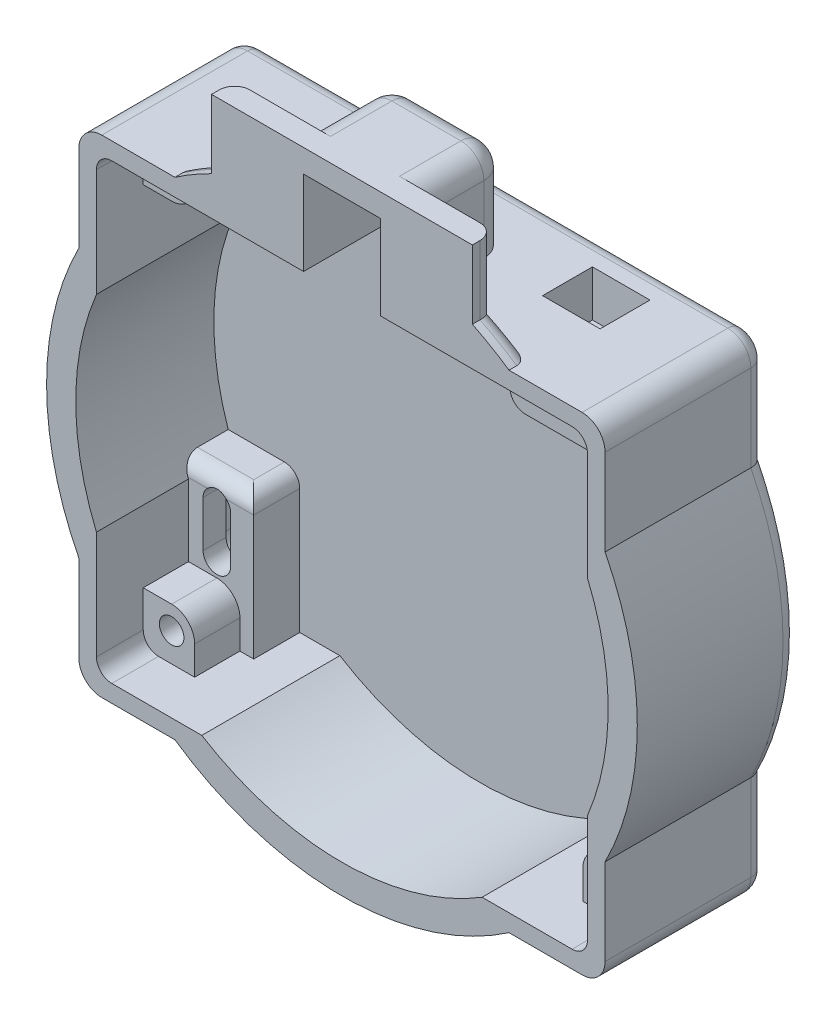
SolidWorks part; units mm, degrees
ref_plane "Front Plane" through (0, 0, 0) normal (0, 0, 1) x (1, 0, 0)
ref_plane "Top Plane" through (0, 0, 0) normal (0, 1, 0) x (1, 0, 0)
ref_plane "Right Plane" through (0, 0, 0) normal (1, 0, 0) x (0, 0, -1)
sketch "Sketch1" plane through (0, 0, 0) normal (0, 0, 1) x (1, 0, 0)
  line L0 (0, 50.5271) -> (0, -52.5058) construction
  line L1 (-17, 43.5) -> (-17, 34.5435)
  line L2 (-17, 43.5) -> (17, 43.5)
  line L3 (17, 43.5) -> (17, 34.5435)
  line L4 (-47.9319, 0) -> (53.9746, 0) construction
  line L5 (-18.2713, 29.5) -> (18.2713, 29.5)
  line L6 (34.3, 31.75) -> (21.7758, 31.75)
  line L7 (34.3, 31.75) -> (34.3, 17.486)
  line L8 (-34.3, 31.75) -> (-34.3, 17.486)
  line L9 (-34.3, 31.75) -> (-21.7758, 31.75)
  line L10 (34.3, -31.75) -> (34.3, -17.486)
  line L11 (34.3, -31.75) -> (21.7758, -31.75)
  line L12 (-34.3, -31.75) -> (-34.3, -17.486)
  line L13 (-34.3, -31.75) -> (-21.7758, -31.75)
  circle A0 centre (0, 0) radius 33.5 construction
  circle A1 centre (0, 0) radius 34.7
  circle A3 centre (0, 0) radius 38.2616 construction
  circle A5 centre (-28.3, 25.75) radius 1.6
  circle A8 centre (28.3, 25.75) radius 1.6
  circle A10 centre (28.3, -25.75) radius 1.6
  circle A12 centre (-28.3, -25.75) radius 1.6
  circle A19 centre (11, 38.1456) radius 1.6 construction
  circle A20 centre (-11, 38.1456) radius 1.6 construction
  arc A21 (21.7758, 31.75) -> (-21.7758, 31.75) centre (0, 0) ccw
  arc A22 (34.3, -17.486) -> (34.3, 17.486) centre (0, 0) ccw
  arc A23 (-21.7758, -31.75) -> (21.7758, -31.75) centre (0, 0) ccw
  arc A24 (-34.3, 17.486) -> (-34.3, -17.486) centre (0, 0) ccw
  dimension "D1" = 67
  dimension "D9" = 3.2
  dimension "D14" = 3.2
  dimension "D3" = 77
  dimension "D2" = 1.2
  dimension "D4" = 34
  dimension "D5" = 10
  dimension "D7" = 25.75
  dimension "D8" = 28.3
  dimension "D12" = 5
  dimension "D13" = 6
  dimension "D15" = 29.5
  dimension "D16" = 6
  dimension "D17" = 6
extrude "Boss-Extrude5" add sketch "Sketch1" along normal blind 3 contours A24 A22 A19 A20 A8 A5 A1 A10 A12 | L1 A20 A19 L3 L2 | L5 A1 | L5 A1 | A12 region at (0, 40.2459, 0) region at (0, 37.4111, 0) region at (0, 31.594, 0) region at (0, -1.1129, 0)
extrude "Boss-Extrude6" add sketch "Sketch1<8>" along normal blind 21 contours L5 A1 | L1 A20 A19 L3 L2 | A24 A22 A19 A20 A8 A5 A1 A10 A12 | A12 region at (0, 40.2459, 0) region at (0, 37.4111, 0) region at (0, 31.594, 0) region at (-28.3, -25.75, 0)
sketch "Sketch1<8>" plane through (0, 0, 0) normal (0, 0, 1) x (1, 0, 0) same geometry as "Sketch1"
sketch "Sketch4" plane through (0, 0, 0) normal (0, 0, -1) x (-1, 0, 0)
  line L7 (-21.7758, 43.5) -> (21.7758, 43.5)
  line L12 (-21.7758, 43.5) -> (-21.7758, 31.75)
  line L13 (-21.7758, 31.75) -> (21.7758, 31.75)
  line L14 (21.7758, 31.75) -> (21.7758, 43.5)
  line L16 (17, 43.5) -> (-17, 43.5) construction
extrude "Cut-Extrude3" cut sketch "Sketch4" against normal blind 7
ref_plane "Plane1" through (0, 43.5, 0) normal (0, 1, 0) x (1, 0, 0)
sketch "Sketch6" plane through (0, 43.5, 0) normal (0, 1, 0) x (1, 0, 0)
  line L1 (-20.5, -9.5) -> (-9.5, -9.5)
  line L2 (-20.5, -9.5) -> (-20.5, -15.5)
  line L3 (-20.5, -15.5) -> (-9.5, -15.5)
  line L4 (-9.5, -9.5) -> (-9.5, -15.5)
  line L5 (-17, -21) -> (17, -21) construction
  line L8 (-31.5, -18.7445) -> (31.5, -18.7445) construction
  line L11 (0, 9.1514) -> (0, -26.2112) construction
  line L12 (21.7758, -7) -> (-21.7758, -7) construction
  line L13 (-7.5, -7) -> (-38.5, -7)
  line L14 (-7.5, -7) -> (-7.5, -18)
  line L15 (-7.5, -18) -> (-38.5, -18)
  line L16 (-38.5, -7) -> (-38.5, -18)
  line L18 (-38.5, 0) -> (-38.5, -21) construction
  line L19 (38.5, -7) -> (38.5, -18)
  line L20 (7.5, -18) -> (38.5, -18)
  line L21 (7.5, -7) -> (38.5, -7)
  line L22 (7.5, -7) -> (7.5, -18)
  line M8 (17, -7) -> (-17, -7)
  line M9 (-17, -7) -> (-17, -21)
  dimension "D1" = 11
  dimension "D2" = 6
  dimension "D3" = 5.5
  dimension "D4" = 63
  dimension "D5" = 22
  dimension "D6" = 2
  dimension "D7" = 3
extrude "Cut-Extrude5" cut sketch "Sketch6" against normal up to surface (11.75 mm away) contours L4 L1 L3 M9 | L2 L3 L1 M9 | L15 L14 L1 L4 L3 M8 M9 | L13 L16 L15 L3 L2 L1 M9 | L19 L20 L22 L21 region at (-28.627, 43.5, 12.5) region at (-18.75, 43.5, 12.5) region at (-16.8547, 43.5, 8.25) region at (-13.25, 43.5, 12.5) up to face at (0, 31.75, 12.25)
extrude "Cut-Extrude6" cut sketch "Sketch6<4>" against normal blind 40 contours L4 L1 L3 M9 | L2 L3 L1 M9 region at (-18.75, 43.5, 12.5) region at (-13.25, 43.5, 12.5)
sketch "Sketch6<4>" plane through (0, 43.5, 0) normal (0, 1, 0) x (1, 0, 0) same geometry as "Sketch6"
sketch "Sketch8" plane through (0, 0, 0) normal (1, 0, 0) x (0, 0, -1)
  line L0 (-7, 31.75) -> (-7, 43.5) construction
  line L1 (-21, 40.5) -> (-10, 40.5)
  line L2 (-21, 40.5) -> (-21, 24.5)
  line L3 (-21, 24.5) -> (-10, 24.5)
  line L4 (-10, 40.5) -> (-10, 24.5)
  line L5 (-7, 43.5) -> (-18, 43.5) construction
  line L6 (-21, 43.5) -> (-21, 34.5435) construction
  dimension "D1" = 3
  dimension "D2" = 16
  dimension "D3" = 3
extrude "Cut-Extrude7" cut sketch "Sketch8" against normal blind 5 and the other way blind 5
sketch "Sketch9" plane through (0, 0, 21) normal (0, 0, 1) x (1, 0, 0)
  line L0 (0, 46.0396) -> (0, -47.6763) construction
  line L1 (-55.9016, 0) -> (68.9785, 0) construction
  line L3 (-32, 29.5) -> (32, 29.5)
  line L4 (-32, 29.5) -> (-32, -29.5)
  line L5 (-32, -29.5) -> (32, -29.5)
  line L6 (32, 29.5) -> (32, -29.5)
  dimension "D1" = 64
  dimension "D2" = 59
extrude "Cut-Extrude8" cut sketch "Sketch9" against normal blind 6.1
sketch "Sketch12" plane through (0, 0, 14.9) normal (0, 0, 1) x (1, 0, 0)
  line L0 (0, 47.9752) -> (0, -48.7077) construction
  line L1 (-25.3, 29.5) -> (-18, 29.5)
  line L2 (-32, 22.75) -> (-32, 11.5)
  line L3 (-32, 11.5) -> (-18, 11.5)
  line L4 (-18, 29.5) -> (-18, 11.5)
  line L5 (-46.551, 0) -> (53.7127, 0) construction
  line L18 (-28.3, 22.75) -> (-32, 22.75)
  line L19 (-25.3, 25.75) -> (-25.3, 29.5)
  line L21 (-32, 29.5) -> (-32, 13.4198) construction
  line L22 (28.3, 22.75) -> (32, 22.75)
  line L23 (25.3, 25.75) -> (25.3, 29.5)
  line L24 (25.3, 29.5) -> (18, 29.5)
  line L25 (18, 29.5) -> (18, 11.5)
  line L26 (32, 11.5) -> (18, 11.5)
  line L27 (32, 22.75) -> (32, 11.5)
  line L28 (-28.3, -22.75) -> (-32, -22.75)
  line L29 (-25.3, -25.75) -> (-25.3, -29.5)
  line L30 (-25.3, -29.5) -> (-18, -29.5)
  line L31 (-18, -29.5) -> (-18, -11.5)
  line L32 (-32, -11.5) -> (-18, -11.5)
  line L33 (-32, -22.75) -> (-32, -11.5)
  line L34 (28.3, -22.75) -> (32, -22.75)
  line L35 (32, -22.75) -> (32, -11.5)
  line L36 (32, -11.5) -> (18, -11.5)
  line L37 (18, -29.5) -> (18, -11.5)
  line L38 (25.3, -29.5) -> (18, -29.5)
  line L39 (25.3, -25.75) -> (25.3, -29.5)
  line L40 (-5, 29.5) -> (-32, 29.5) construction
  arc A0 (-28.3, 22.75) -> (-25.3, 25.75) centre (-28.3, 25.75) ccw
  arc A5 (28.3, 22.75) -> (25.3, 25.75) centre (28.3, 25.75) cw
  arc A6 (-28.3, -22.75) -> (-25.3, -25.75) centre (-28.3, -25.75) cw
  arc A7 (28.3, -22.75) -> (25.3, -25.75) centre (28.3, -25.75) ccw
  dimension "D1" = 6
  dimension "D2" = 18
  dimension "D3" = 14
  dimension "D4" = 29.5
extrude "Cut-Extrude11" cut sketch "Sketch12" against normal up to surface (11.9 mm away) up to face at (0, -2.6, 3)
sketch "Sketch13" plane through (0, 0, 0) normal (0, 0, -1) x (-1, 0, 0)
  line L0 (34.3, -31.75) -> (23.5, -31.75)
  line L1 (34.3, -31.75) -> (21.7758, -31.75) construction
  line L2 (23.5, -31.75) -> (23.5, -11.25)
  line L3 (23.5, -11.25) -> (36.8197, -11.25)
  line L4 (34.3, -31.75) -> (34.3, -17.486)
  line L5 (28.3, -20.55) -> (28.3, -14.55) construction
  line L6 (26.5, -20.55) -> (26.5, -14.55)
  line L7 (30.1, -20.55) -> (30.1, -14.55)
  line L9 (25.05, -11.8) -> (31.55, -11.8)
  line L10 (25.05, -11.8) -> (25.05, -23.3)
  line L11 (25.05, -23.3) -> (31.55, -23.3)
  line L12 (31.55, -11.8) -> (31.55, -23.3)
  line L13 (25.05, -11.8) -> (31.55, -23.3) construction
  line L14 (25.05, -23.3) -> (31.55, -11.8) construction
  arc A0 (34.3, -17.486) -> (34.3, 17.486) centre (0, 0) ccw construction
  arc A1 (36.8197, -11.25) -> (34.3, -17.486) centre (0, 0) cw
  arc A2 (26.5, -20.55) -> (30.1, -20.55) centre (28.3, -20.55) ccw
  arc A3 (30.1, -14.55) -> (26.5, -14.55) centre (28.3, -14.55) ccw
  point P13 (28.3, -12.75)
  point P17 (28.3, -17.55)
  point P23 (28.3, -22.35)
  point P25 (28.3, -17.55)
  line M16 (21.7758, -31.75) -> (34.3, -31.75)
  line M17 (34.3, -31.75) -> (34.3, -17.486)
  arc M18 (34.3, -17.486) -> (34.3, 17.486) centre (0, 0) ccw
  dimension "D2" = 9.6
  dimension "D1" = 3.6
  dimension "D3" = 3
  dimension "D4" = 1.5
  dimension "D5" = 3.4
  dimension "D6" = 6.5
  dimension "D7" = 11.5
extrude "Boss-Extrude8" add sketch "Sketch13" against normal blind 6 from offset 3 contours L3 L2 L9 L12 L11 L10 M16 M17 M18 | L12 L9 L10 L11 A3 L7 A2 L6 | L7 A3 L6 A2 region at (-28.9, -31.5055, 0) region at (-28.3, -17.55, 0) region at (-28.3, -11.9321, 0) offset against normal yes
extrude "Cut-Extrude12" cut sketch "Sketch13<4>" against normal through all contours L7 A3 L6 A2 region at (-28.3, -17.55, 0)
sketch "Sketch13<4>" plane through (0, 0, 0) normal (0, 0, -1) x (-1, 0, 0) same geometry as "Sketch13"
extrude "Cut-Extrude13" cut sketch "Sketch13<6>" against normal blind 6 contours L12 L9 L10 L11 A3 L7 A2 L6 region at (-28.3, -11.9321, 0)
sketch "Sketch13<6>" plane through (0, 0, 0) normal (0, 0, -1) x (-1, 0, 0) same geometry as "Sketch13"
sketch "Sketch15" plane through (0, 31.75, 0) normal (0, 1, 0) x (1, 0, 0)
  line L0 (32, -14.9) -> (25.3, -14.9) construction
  line L1 (13.3, 0) -> (25.3, 0)
  line L2 (13.3, 0) -> (13.3, -12.4)
  line L3 (13.3, -12.4) -> (25.3, -12.4)
  line L4 (25.3, 0) -> (25.3, -12.4)
  line L5 (25.3, -3) -> (25.3, -14.9) construction
  line L6 (-21.7758, 0) -> (21.7758, 0) construction
  line L7 (19.3, -12.4) -> (19.3, -2.9681) construction
  line L8 (16.4, -4.6) -> (22.2, -4.6)
  line L9 (16.4, -4.6) -> (16.4, -10.4)
  line L10 (16.4, -10.4) -> (22.2, -10.4)
  line L11 (22.2, -4.6) -> (22.2, -10.4)
  line L12 (16.4, -10.4) -> (15.55, -10.4)
  line L13 (15.55, -10.4) -> (15.55, -3.9)
  line L14 (15.55, -3.9) -> (23.05, -3.9)
  line L15 (23.05, -3.9) -> (23.05, -10.4)
  line L16 (23.05, -10.4) -> (22.2, -10.4)
  line M39 (34.3, 0) -> (-34.3, 0)
  dimension "D1" = 2.5
  dimension "D2" = 12
  dimension "D3" = 5.8
  dimension "D4" = 7.5
  dimension "D5" = 6.5
  dimension "D6" = 2
extrude "Boss-Extrude10" add sketch "Sketch15" against normal blind 12.5 contours L10 L7 L8 L9 | L7 L10 L11 L8 | L8 L7 L14 L13 L12 L9 | L7 L8 L11 L16 L15 L14 | L4 L2 L3 L10 L12 L13 L14 L15 L16 M39 region at (17.85, 31.75, 7.5) region at (20.75, 31.75, 7.5) region at (19.3, 31.75, 0.1726) region at (17.85, 31.75, 4.525) region at (19.375, 31.75, 4.25)
extrude "Cut-Extrude14" cut sketch "Sketch15<3>" against normal blind 6 contours L8 L7 L14 L13 L12 L9 | L7 L8 L11 L16 L15 L14 region at (17.85, 31.75, 4.525) region at (19.375, 31.75, 4.25)
sketch "Sketch15<3>" plane through (0, 31.75, 0) normal (0, 1, 0) x (1, 0, 0) same geometry as "Sketch15"
extrude "Cut-Extrude15" cut sketch "Sketch15<4>" against normal up to next contours L7 L10 L11 L8 | L10 L7 L8 L9 region at (17.85, 31.75, 7.5) region at (20.75, 31.75, 7.5)
sketch "Sketch15<4>" plane through (0, 31.75, 0) normal (0, 1, 0) x (1, 0, 0) same geometry as "Sketch15"
extrude "Cut-Extrude16" cut sketch "Sketch1<9>" along normal through all contours A12 region at (-28.3, -25.75, 0)
sketch "Sketch1<9>" plane through (0, 0, 0) normal (0, 0, 1) x (1, 0, 0) same geometry as "Sketch1"
fillet "Fillet1" radius 3 11 edges at (-34.3, 31.75, 10.5) (-34.3, -31.75, 10.5) (34.3, -31.75, 10.5) (34.3, 31.75, 10.5) (-7.5, 37.625, 7) (7.5, 37.625, 7) (0, 43.5, 7) (-7.5, 43.5, 12.5) (7.5, 43.5, 12.5) (0, 29.5, 10) (0, 40.5, 10)
fillet "Fillet3" radius 2 4 edges at (-32, -29.5, 17.95) (32, -29.5, 17.95) (32, 29.5, 17.95) (-32, 29.5, 17.95)
fillet "Fillet6" radius 2 18 edges at (-34.3, -23.118, 0) (-33.4213, -30.8713, 0) (26.5379, -31.75, 0) (33.4213, -30.8713, 0) (-34.3, 23.118, 0) (-33.4213, 30.8713, 0) (34.3, 23.118, 0) (33.4213, 30.8713, 0) (-38.5, 0, 0) (-26.5379, -31.75, 0) (0, -38.5, 0) (34.3, -23.118, 0) (38.5, 0, 0) (0, 31.75, 0) (19.4382, 33.2326, 18) (-19.4382, 33.2326, 18) (-17, 39.0217, 18) (17, 39.0217, 18) tangent propagation no
fillet "Fillet7" radius 2 8 edges at (-31.55, -11.8, 3) (-31.55, -23.3, 3) (-25.05, -11.8, 3) (-25.05, -23.3, 3) (-28.1629, -11.25, 9) (-23.5, -11.25, 6) (25.3, 19.25, 7.7) (13.3, 19.25, 7.7)
equation "\"ScrewHole\"= 3.2"
equation "\"D9@Sketch1\"=\"ScrewHole\""
